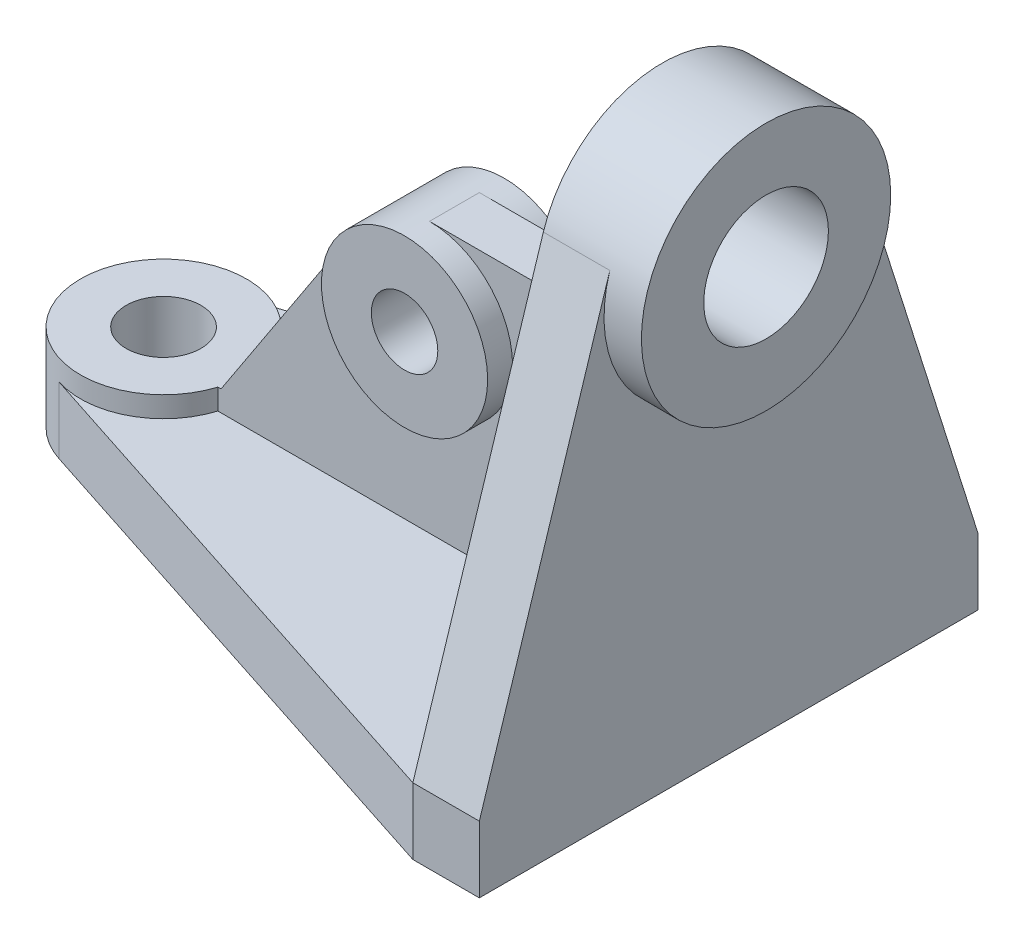
SolidWorks part; units mm, degrees
ref_plane "Front Plane" through (0, 0, 0) normal (0, 0, 1) x (1, 0, 0)
ref_plane "Top Plane" through (0, 0, 0) normal (0, 1, 0) x (1, 0, 0)
ref_plane "Right Plane" through (0, 0, 0) normal (1, 0, 0) x (0, 0, -1)
sketch "Sketch1" plane through (0, 0, 0) normal (0, 1, 0) x (1, 0, 0)
  line L0 (0, 0) -> (120, 0) construction
  line L1 (120, -60) -> (120, 60)
  line L2 (120, 60) -> (-6.1777, 19.022)
  line L3 (120, -60) -> (-6.1777, -19.022)
  line L4 (120, 60) -> (136, 60)
  line L5 (136, 60) -> (136, -60)
  line L6 (136, -60) -> (120, -60)
  circle A0 centre (0, 0) radius 9
  circle A1 centre (0, 0) radius 20
  point P8 (120, 0)
  dimension "D1" = 40
  dimension "D2" = 18
  dimension "D3" = 120
  dimension "D4" = 120
  dimension "D5" = 16
extrude "Boss-Extrude1" add sketch "Sketch1" along normal blind 21 contours A0 A1 region at (-19.4343, 0, 0)
extrude "Boss-Extrude2" add sketch "Sketch1<3>" along normal blind 16 contours L0 A1 L3 L1 | A1 L0 L1 L2 | L6 L5 L4 L1 region at (73.8068, 0, -22.7388) region at (73.8068, 0, 22.7388) region at (128, 0, 0)
sketch "Sketch1<3>" plane through (0, 0, 0) normal (0, 1, 0) x (1, 0, 0) same geometry as "Sketch1"
sketch "Sketch2" plane through (136, 0, 0) normal (1, 0, 0) x (0, 0, -1)
  line L0 (-60, 16) -> (-28.5976, 115.0651)
  line L1 (60, 16) -> (28.5976, 115.0651)
  line L2 (-60, 16) -> (60, 16)
  circle A0 centre (0, 106) radius 30
  circle A1 centre (0, 106) radius 15
  line M3 (60, 16) -> (-60, 16)
  dimension "D1" = 30
  dimension "D2" = 60
  dimension "D3" = 90
extrude "Boss-Extrude3" add sketch "Sketch2" against normal blind 16 contours A0 L0 L1 M3 region at (136, 48.7404, 0)
extrude "Boss-Extrude4" add sketch "Sketch2<3>" along normal blind 25 from offset 16 contours A0 A1 region at (136, 135.1515, 0) offset against normal yes
sketch "Sketch2<3>" plane through (136, 0, 0) normal (1, 0, 0) x (0, 0, -1) same geometry as "Sketch2"
sketch "gurt" plane through (0, 0, 0) normal (0, 0, 1) x (1, 0, 0)
  line L0 (120, 16) -> (-6.1777, 16) construction
  line L1 (70, 81) -> (120, 81)
  line L2 (120, 16) -> (120, 115.0651) construction
  line L4 (120, 81) -> (120, 16)
  line L6 (19.8386, 21) -> (53.2774, 71.9707)
  line L7 (20, 21) -> (-20, 21) construction
  line L8 (19.8386, 21) -> (19.8386, 16)
  line L9 (19.8386, 16) -> (120, 16)
  circle A0 centre (70, 61) radius 20
  circle A1 centre (70, 61) radius 8
  dimension "D1" = 40
  dimension "D2" = 16
  dimension "D3" = 45
  dimension "D4" = 70
extrude "Boss-Extrude5" add sketch "gurt" along normal mid plane 24 separate body contours A0 A1 region at (83.7421, 74.7421, 0)
extrude "Boss-Extrude6" add sketch "gurt<4>" along normal mid plane 12 contours A0 L6 L8 L9 L4 L1 region at (80.7003, 40.8507, 0)
sketch "gurt<4>" plane through (0, 0, 0) normal (0, 0, 1) x (1, 0, 0) same geometry as "gurt"
sketch "Sketch4" plane through (0, 16, 0) normal (0, 1, 0) x (1, 0, 0)
  line L3 (19.8386, 2.5358) -> (19.8386, 6)
  line L4 (19.8386, 6) -> (18.9363, 6)
  line L5 (18.9363, 6) -> (19.8386, 2.5358)
  line L6 (-74.8, 0) -> (74.8, 0) construction
  line L7 (19.8386, -6) -> (18.9363, -6)
  line L8 (19.8386, -2.5358) -> (19.8386, -6)
  line L9 (18.9363, -6) -> (19.8386, -2.5358)
extrude "Boss-Extrude7" add sketch "Sketch4" along normal blind 5
